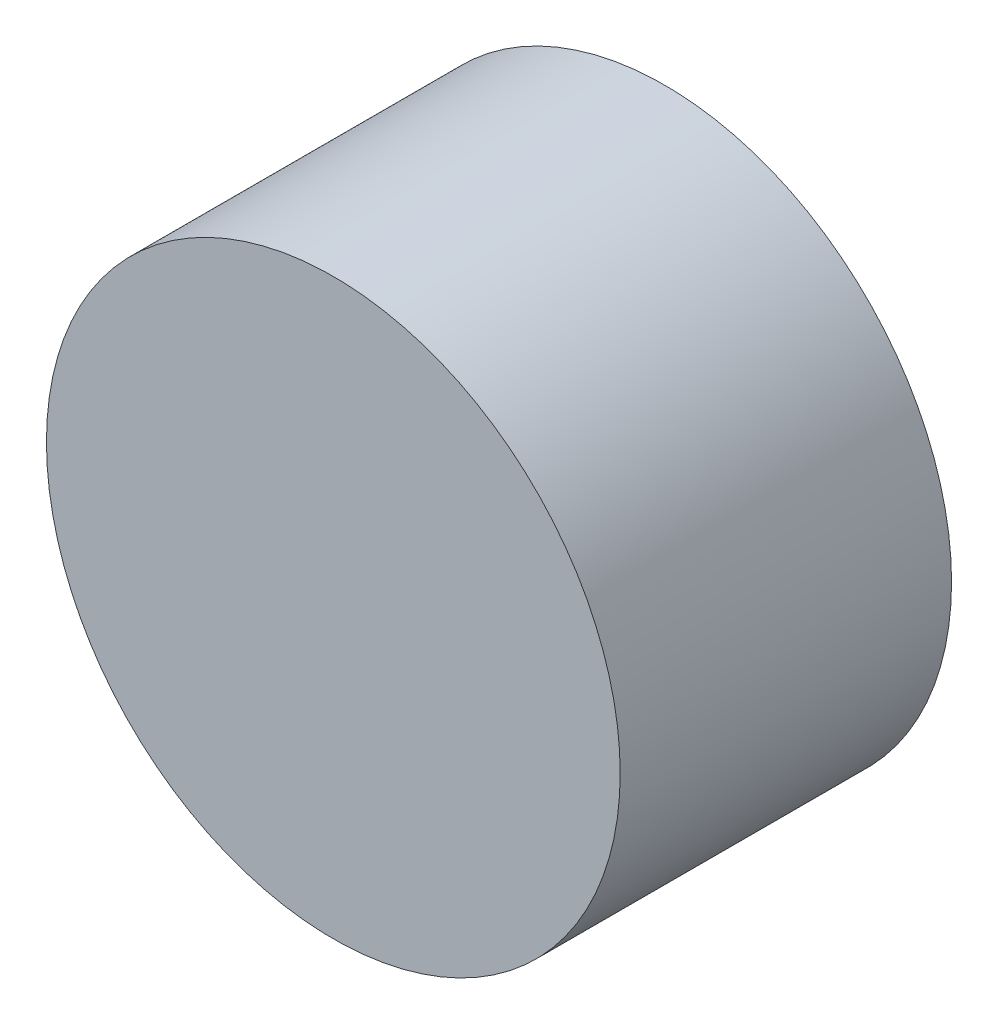
SolidWorks part; units mm, degrees
material "Pure Lead"
ref_plane "XY" through (0, 0, 0) normal (0, 0, 1) x (1, 0, 0)
ref_plane "XZ" through (0, 0, 0) normal (0, 1, 0) x (1, 0, 0)
ref_plane "YZ" through (0, 0, 0) normal (1, 0, 0) x (0, 0, -1)
ref_axis "X" through (-27.94, 0, 0) along (1, 0, 0)
ref_axis "Y" through (0, -27.94, 0) along (0, 1, 0)
ref_axis "Z" through (0, 0, 33.3375) along (0, 0, -1)
sketch "Sketch1" plane through (0, 0, 0) normal (0, 0, 1) x (1, 0, 0)
  circle A0 centre (0, 0) radius 25.4
  dimension "D1" = 50.8
extrude "Boss-Extrude1" add sketch "Sketch1" along normal blind 29.337
